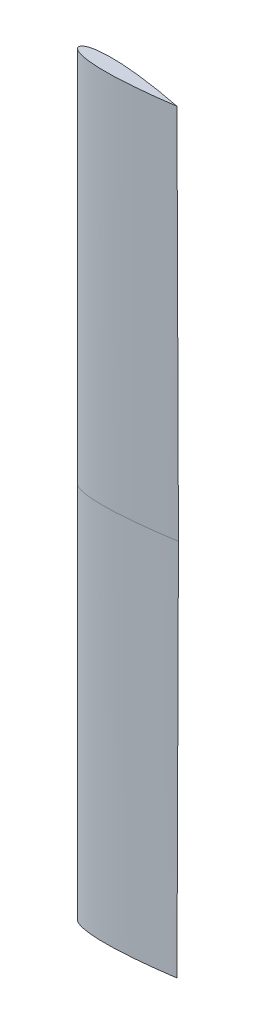
SolidWorks part; units mm, degrees
ref_plane "Front Plane" through (0, 0, 0) normal (0, 0, 1) x (1, 0, 0)
ref_plane "Top Plane" through (0, 0, 0) normal (0, 1, 0) x (1, 0, 0)
ref_plane "Right Plane" through (0, 0, 0) normal (1, 0, 0) x (0, 0, -1)
sketch "rootSketch" plane through (0, 0, 0) normal (0, 1, 0) x (1, 0, 0)
  line L0 (0, 0) -> (1500, 0) construction
  line L2 (12.9584, -4.0359) -> (13.0401, 3.7637) construction
  line L3 (0, 0) -> (51.9971, -0.5445) construction
  spline S0 degree 4 poles (0, 0) (0, 0.0566) (0.0054, 0.1482) (0.026, 0.2795) (0.0773, 0.4498) (0.1458, 0.6077) (0.2462, 0.7799) (0.3892, 0.9697) (0.5954, 1.1857) (0.9012, 1.439) (1.3642, 1.74) (2.0702, 2.0939) (3.1645, 2.5052) (4.8013, 2.9431) (7.2463, 3.3729) (10.4047, 3.6692) (14.0938, 3.7814) (18.1158, 3.7074) (21.6283, 3.5188) (24.637, 3.2896) (27.6374, 3.0166) (30.1424, 2.7545) (32.6295, 2.467) (35.6353, 2.087) (38.5971, 1.6865) (41.6282, 1.2387) (44.5383, 0.7801) (47.1162, 0.3449) (48.9115, 0.033) (51.4229, -0.4309) (52.8543, -0.7076) (54.9428, -1.1255) (55.96, -1.3444) (56.786, -1.518) (56.9962, -1.5665) (57.2091, -1.6117) knots 0 0 0 0 0 0.003844 0.006241 0.009008 0.01207 0.015524 0.019766 0.025141 0.032337 0.04248 0.057257 0.078755 0.111734 0.157569 0.225948 0.294326 0.362704 0.431082 0.465271 0.49946 0.567838 0.602027 0.636216 0.704594 0.772972 0.807161 0.84135 0.875539 0.909728 0.954864 0.977432 0.988716 1 1 1 1 1 construction
  spline S1 degree 4 poles (0, 0) (0, 0.0566) (0.0054, 0.1482) (0.026, 0.2795) (0.0773, 0.4498) (0.1458, 0.6077) (0.2462, 0.7799) (0.3892, 0.9697) (0.5954, 1.1857) (0.9012, 1.439) (1.3642, 1.74) (2.0702, 2.0939) (3.1645, 2.5052) (4.8013, 2.9431) (7.2463, 3.3729) (10.4047, 3.6692) (14.0938, 3.7814) (18.1158, 3.7074) (21.6283, 3.5188) (24.637, 3.2896) (27.6374, 3.0166) (30.1424, 2.7545) (32.6295, 2.467) (35.6353, 2.087) (38.5971, 1.6865) (41.6282, 1.2387) (44.5383, 0.7801) (47.1162, 0.3449) (48.9115, 0.033) (50.6554, -0.2891) (51.551, -0.4583) (52, -0.5446) knots 0 0 0 0 0 0.003844 0.006241 0.009008 0.01207 0.015524 0.019766 0.025141 0.032337 0.04248 0.057257 0.078755 0.111734 0.157569 0.225948 0.294326 0.362704 0.431082 0.465271 0.49946 0.567838 0.602027 0.636216 0.704594 0.772972 0.807161 0.84135 0.875539 0.909728 0.909728 0.909728 0.909728 0.909728
  spline S2 degree 4 poles (0, 0) (-0.0012, -0.0566) (0.0023, -0.1483) (0.0202, -0.28) (0.0679, -0.4513) (0.1331, -0.6106) (0.2298, -0.7848) (0.3688, -0.9777) (0.5704, -1.1979) (0.8709, -1.4575) (1.3275, -1.7682) (2.0259, -2.1368) (3.1114, -2.5709) (4.7387, -3.043) (7.1741, -3.5239) (10.3256, -3.8863) (14.0115, -4.0757) (18.0342, -4.086) (21.5498, -3.971) (24.5627, -3.8048) (27.5681, -3.5948) (30.0781, -3.3851) (32.5707, -3.1498) (35.5838, -2.8329) (38.5533, -2.4945) (41.5931, -2.1102) (44.5122, -1.7127) (47.0986, -1.3315) (48.9001, -1.0574) (51.4206, -0.6461) (52.8575, -0.3995) (54.9543, -0.0254) (55.9759, 0.1722) (56.8054, 0.3284) (57.0166, 0.3726) (57.2303, 0.4133) knots 0 0 0 0 0 0.003844 0.006241 0.009008 0.01207 0.015524 0.019766 0.025141 0.032337 0.04248 0.057257 0.078755 0.111734 0.157569 0.225948 0.294326 0.362704 0.431082 0.465271 0.49946 0.567838 0.602027 0.636216 0.704594 0.772972 0.807161 0.84135 0.875539 0.909728 0.954864 0.977432 0.988716 1 1 1 1 1 construction
  spline S3 degree 4 poles (0, 0) (-0.0012, -0.0566) (0.0023, -0.1483) (0.0202, -0.28) (0.0679, -0.4513) (0.1331, -0.6106) (0.2298, -0.7848) (0.3688, -0.9777) (0.5704, -1.1979) (0.8709, -1.4575) (1.3275, -1.7682) (2.0259, -2.1368) (3.1114, -2.5709) (4.7387, -3.043) (7.1741, -3.5239) (10.3256, -3.8863) (14.0115, -4.0757) (18.0342, -4.086) (21.5498, -3.971) (24.5627, -3.8048) (27.5681, -3.5948) (30.0781, -3.3851) (32.5707, -3.1498) (35.5838, -2.8329) (38.5533, -2.4945) (41.5931, -2.1102) (44.5122, -1.7127) (47.0986, -1.3315) (48.9001, -1.0574) (50.6504, -0.7718) (51.5493, -0.6214) (52, -0.5446) knots 0 0 0 0 0 0.003844 0.006241 0.009008 0.01207 0.015524 0.019766 0.025141 0.032337 0.04248 0.057257 0.078755 0.111734 0.157569 0.225948 0.294326 0.362704 0.431082 0.465271 0.49946 0.567838 0.602027 0.636216 0.704594 0.772972 0.807161 0.84135 0.875539 0.909728 0.909728 0.909728 0.909728 0.909728
  point P10 (12.9993, -0.1361)
  dimension "incidenceAngle" = 0.6
  dimension "rootChord" = 52
  dimension "rootQuarterChord" = 13
  dimension "rootMaxThickness" = 7.8
ref_plane "Plane1" through (0, 195, 0) normal (0, 1, 0) x (1, 0, 0)
sketch "tipSketch" plane through (0, 195, 0) normal (0, 1, 0) x (1, 0, 0)
  line L0 (218.7894, 0) -> (520.1012, 0) construction
  line L3 (0, 0) -> (51.9836, -1.3068) construction
  line L4 (12.8979, -4.2255) -> (13.0939, 3.5721) construction
  spline S0 degree 4 poles (0, 0) (0, 0.0567) (0.0054, 0.1484) (0.0262, 0.28) (0.0777, 0.45) (0.1467, 0.6074) (0.2474, 0.778) (0.3899, 0.9647) (0.5942, 1.1755) (0.8949, 1.4208) (1.3529, 1.7136) (2.0534, 2.0565) (3.1406, 2.4515) (4.773, 2.8669) (7.2164, 3.2635) (10.3766, 3.5157) (14.0723, 3.5751) (18.1023, 3.4425) (21.6194, 3.2024) (24.632, 2.9288) (27.1334, 2.6647) (29.1413, 2.4316) (31.6284, 2.1222) (34.1465, 1.7785) (36.6056, 1.4223) (39.6413, 0.9495) (42.5322, 0.4793) (45.6741, -0.0766) (48.4074, -0.5843) (51.4046, -1.1813) (52.8681, -1.4856) (54.929, -1.9284) (55.9706, -2.1673) (56.7784, -2.3492) (57.0008, -2.4034) (57.2081, -2.4505) knots 0 0 0 0 0 0.003846 0.006245 0.009023 0.012045 0.015501 0.01968 0.024954 0.031954 0.041824 0.056556 0.077861 0.110456 0.156157 0.224645 0.293132 0.36162 0.430108 0.464352 0.498596 0.53284 0.567084 0.635571 0.669815 0.704059 0.772547 0.841035 0.875279 0.909523 0.954761 0.977381 0.98869 1 1 1 1 1 construction
  spline S1 degree 4 poles (0, 0) (0, 0.0567) (0.0054, 0.1484) (0.0262, 0.28) (0.0777, 0.45) (0.1467, 0.6074) (0.2474, 0.778) (0.3899, 0.9647) (0.5942, 1.1755) (0.8949, 1.4208) (1.3529, 1.7136) (2.0534, 2.0565) (3.1406, 2.4515) (4.773, 2.8669) (7.2164, 3.2635) (10.3766, 3.5157) (14.0723, 3.5751) (18.1023, 3.4425) (21.6194, 3.2024) (24.632, 2.9288) (27.1334, 2.6647) (29.1413, 2.4316) (31.6284, 2.1222) (34.1465, 1.7785) (36.6056, 1.4223) (39.6413, 0.9495) (42.5322, 0.4793) (45.6741, -0.0766) (48.4074, -0.5843) (50.6605, -1.0331) (51.5513, -1.2144) (52, -1.3072) knots 0 0 0 0 0 0.003846 0.006245 0.009023 0.012045 0.015501 0.01968 0.024954 0.031954 0.041824 0.056556 0.077861 0.110456 0.156157 0.224645 0.293132 0.36162 0.430108 0.464352 0.498596 0.53284 0.567084 0.635571 0.669815 0.704059 0.772547 0.841035 0.875279 0.909523 0.909523 0.909523 0.909523 0.909523
  spline S2 degree 4 poles (0, 0) (-0.0029, -0.0566) (-0.0021, -0.1485) (0.012, -0.281) (0.055, -0.4533) (0.116, -0.614) (0.208, -0.7894) (0.3409, -0.9831) (0.5343, -1.2039) (0.8224, -1.464) (1.2651, -1.7794) (1.9475, -2.1571) (3.0134, -2.6062) (4.623, -3.1031) (7.0433, -3.6219) (10.1869, -4.0326) (13.8749, -4.2776) (17.9065, -4.3477) (21.4312, -4.2846) (24.4537, -4.1627) (26.9652, -4.0246) (28.9823, -3.8927) (31.4818, -3.7087) (34.014, -3.4919) (36.4879, -3.2598) (39.5435, -2.94) (42.4544, -2.6157) (45.6203, -2.2183) (48.3756, -1.8486) (51.399, -1.403) (52.876, -1.1726) (54.9565, -0.8339) (56.0088, -0.6476) (56.8247, -0.5066) (57.0496, -0.4636) (57.259, -0.4269) knots 0 0 0 0 0 0.003846 0.006245 0.009023 0.012045 0.015501 0.01968 0.024954 0.031954 0.041824 0.056556 0.077861 0.110456 0.156157 0.224645 0.293132 0.36162 0.430108 0.464352 0.498596 0.53284 0.567084 0.635571 0.669815 0.704059 0.772547 0.841035 0.875279 0.909523 0.954761 0.977381 0.98869 1 1 1 1 1 construction
  spline S3 degree 4 poles (0, 0) (-0.0029, -0.0566) (-0.0021, -0.1485) (0.012, -0.281) (0.055, -0.4533) (0.116, -0.614) (0.208, -0.7894) (0.3409, -0.9831) (0.5343, -1.2039) (0.8224, -1.464) (1.2651, -1.7794) (1.9475, -2.1571) (3.0134, -2.6062) (4.623, -3.1031) (7.0433, -3.6219) (10.1869, -4.0326) (13.8749, -4.2776) (17.9065, -4.3477) (21.4312, -4.2846) (24.4537, -4.1627) (26.9652, -4.0246) (28.9823, -3.8927) (31.4818, -3.7087) (34.014, -3.4919) (36.4879, -3.2598) (39.5435, -2.94) (42.4544, -2.6157) (45.6203, -2.2183) (48.3756, -1.8486) (50.6484, -1.5136) (51.5472, -1.3773) (52, -1.3072) knots 0 0 0 0 0 0.003846 0.006245 0.009023 0.012045 0.015501 0.01968 0.024954 0.031954 0.041824 0.056556 0.077861 0.110456 0.156157 0.224645 0.293132 0.36162 0.430108 0.464352 0.498596 0.53284 0.567084 0.635571 0.669815 0.704059 0.772547 0.841035 0.875279 0.909523 0.909523 0.909523 0.909523 0.909523
  point P10 (12.9959, -0.3267)
  dimension "incidenceAngle" = 1.44
  dimension "tipChord" = 52
  dimension "tipQuarterChord" = 13
  dimension "tipMaxThickness" = 7.8
  dimension "sweepOffset" = 0
loft "Loft1" add profiles "rootSketch", "tipSketch" connector at (0, 0, 0) connector at (0, 195, 0)
mirror "Mirror1" about plane through (0, 0, 0) normal (0, 1, 0) of "Loft1"
ref_plane "Plane2" through (52, 0, 0) normal (1, 0, 0) x (0, 0, -1)
sketch "elevatorSketch" plane through (0, 0, 0) normal (0, 0, 1) x (1, 0, 0)
  line L0 (31.59, 0) -> (31.59, 145.86)
  line L1 (0, 146.25) -> (31.2, 146.25) construction
  line L2 (0, 0) -> (31.2, 0) construction
  line L3 (-0.0003, 0) -> (52, 0) construction
  line L4 (31.2, 0) -> (31.2, 146.25)
  line L5 (31.59, 145.86) -> (83.2, 145.86)
  line L7 (31.2, 146.25) -> (83.2, 146.25)
  line L8 (31.2, 0) -> (31.59, 0)
  line L9 (83.2, 146.25) -> (83.2, 145.86)
  dimension "elevatorEndyLoc" = 146.25
  dimension "elevatorEndxLoc" = 31.2
  dimension "D1" = 31.2
  dimension "D2" = 52
  dimension "D3" = 0.39
extrude "Cut-Extrude2" [suppressed] cut sketch "elevatorSketch" against normal blind 200 and the other way blind 200 contours L0 L5 L9 L7 L4 L8
mirror "Mirror2" [suppressed] about plane through (0, 0, 0) normal (0, 1, 0)
equation "\"rootChord@rootSketch\"=(\"rootChord\"+\"rootChord\")/2"
equation "\"rootQuarterChord@rootSketch\" = \"rootChord@rootSketch\" / 4"
equation "\"rootMaxThickness@rootSketch\" = \"rootChord\" * \"NACAairfoil\" / 100"
equation "\"halfSpan@Plane1\"=\"halfSpan\""
equation "\"tipQuarterChord@tipSketch\"=\"tipChord@tipSketch\"/4"
equation "\"tipMaxThickness@tipSketch\"=\"tipChord@tipSketch\"*\"NACAairfoil\"/100"
equation "\"rootChord@Plane2\"=\"rootChord@rootSketch\""
equation "\"elevatorWidth\"= 0.75'Elevator width as a percentage of H-stab span"
equation "\"elevatorEndyLoc@elevatorSketch\"=\"elevatorWidth\"*\"halfSpan@Plane1\""
equation "\"elevatorEndxLoc@elevatorSketch\"=\"elevatorEndyLoc@elevatorSketch\" * tan ( \"sweepAngle\" )  + 0.6 *  ( \"rootChord@rootSketch\" + \"elevatorEndyLoc@elevatorSketch\" *  (  (  ( \"tipChord@tipSketch\" - \"rootChord@rootSketch\" )  / \"halfSpan@Plane1\" )  )  )"
equation "\"D1@elevatorSketch\"=0.6*\"rootChord@rootSketch\""
equation "\"D2@elevatorSketch\"=1*\"rootChord@rootSketch\""
equation "\"D3@elevatorSketch\" = \"halfSpan\" / 500"
equation "\"halfSpan\"= \"rootChord\" * ( 1 + \"taperRatio\" ) / 2 * \"aspectRatio\" / 2'H-stab half Span"
equation "\"sweepOffset@tipSketch\" = \"halfSpan\" * tan ( \"sweepAngle\" ) "
equation "\"incidenceAngle@rootSketch\"=\"incidentAngle\""
equation "\"rootChord\"= 0.052"
equation "\"NACAairfoil\"= 0015"
equation "\"incidentAngle\"= 0.6"
equation "\"aspectRatio\"= 7.5"
equation "\"taperRatio\"= 1"
equation "\"sweepAngle\"= 0"
equation "\"tipChord@tipSketch\"=\"rootChord\"*\"taperRatio\""
